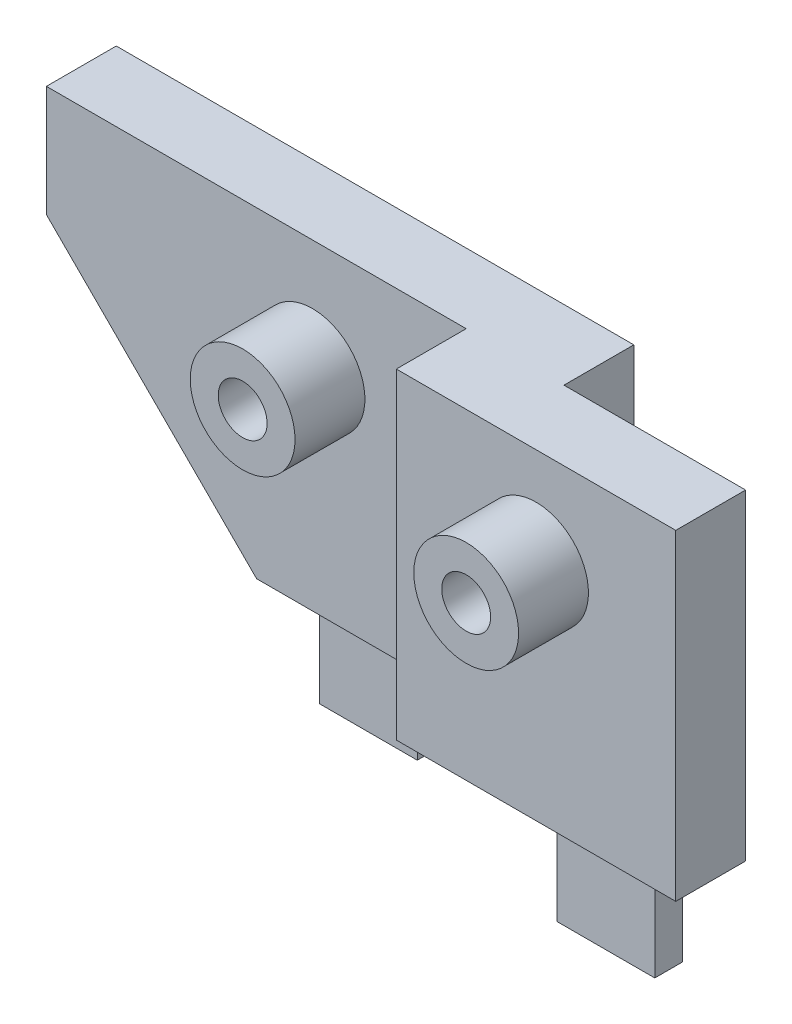
SolidWorks part; units mm, degrees
ref_plane "Front Plane" through (0, 0, 0) normal (0, 0, 1) x (1, 0, 0)
ref_plane "Top Plane" through (0, 0, 0) normal (0, 1, 0) x (1, 0, 0)
ref_plane "Right Plane" through (0, 0, 0) normal (1, 0, 0) x (0, 0, -1)
sketch "Sketch1" plane through (0, 0, 0) normal (0, 1, 0) x (1, 0, 0)
  line L0 (18, 0) -> (22, 0)
  line L1 (0, 0) -> (18, 0)
  line L2 (0, 0) -> (0, -5)
  line L3 (0, -5) -> (15, -5)
  line L4 (18, 0) -> (18, -10) construction
  line L5 (22, -5) -> (35, -5)
  line L6 (15, -5) -> (15, -10)
  line L7 (15, -10) -> (35, -10)
  line L8 (35, -5) -> (35, -10)
  line L9 (22, 0) -> (22, -5)
  dimension "D1" = 5
  dimension "D2" = 18
  dimension "D3" = 5
  dimension "D4" = 20
  dimension "D5" = 15
  dimension "D6" = 5
  dimension "D7" = 7
extrude "Boss-Extrude1" add sketch "Sketch1" along normal blind 23
sketch "Sketch2" plane through (0, 0, 10) normal (0, 0, 1) x (1, 0, 0)
  line L0 (35, 16) -> (25, 16) construction
  line L1 (35, 23) -> (35, 0) construction
  line L2 (15, 0) -> (35, 0) construction
  line L3 (0, 23) -> (0, 0) construction
  line L4 (0, 0) -> (15, 0) construction
  circle A0 centre (4, 15) radius 1.75
  circle A1 centre (25, 16) radius 1.75
  dimension "D5" = 3.5
  dimension "D6" = 3.5
  dimension "D1" = 10
  dimension "D2" = 16
  dimension "D3" = 4
  dimension "D4" = 15
extrude "Cut-Extrude1" cut sketch "Sketch2" against normal blind 10
sketch "Sketch3" plane through (0, 0, 0) normal (0, -1, 0) x (1, 0, 0)
  line L0 (15, 5) -> (22, 5) construction
  line L1 (18.5, 0) -> (18.5, 10) construction
  line L2 (22, 0) -> (0, 0) construction
  line L3 (15, 10) -> (35, 10) construction
  circle A0 centre (18.5, 5) radius 1.5
  point P10 (18.5, 5)
  dimension "D1" = 3
extrude "Cut-Extrude2" cut sketch "Sketch3" against normal blind 10 contours A0
sketch "Sketch4" plane through (0, 0, 0) normal (0, -1, 0) x (1, 0, 0)
  line L0 (0, 2.5) -> (22, 2.5) construction
  line L1 (0, 0) -> (0, 5) construction
  line L2 (22, 5) -> (22, 0) construction
  line L3 (15, 7.5) -> (35, 7.5) construction
  line L4 (15, 5) -> (15, 10) construction
  line L5 (35, 10) -> (35, 5) construction
  line L6 (22, 0) -> (0, 0) construction
  line L7 (10, 1.5) -> (3, 1.5)
  line L8 (10, 1.5) -> (10, 3.5)
  line L9 (10, 3.5) -> (3, 3.5)
  line L10 (3, 1.5) -> (3, 3.5)
  line L11 (10, 1.5) -> (3, 3.5) construction
  line L12 (10, 3.5) -> (3, 1.5) construction
  line L13 (32, 6.5) -> (25, 6.5)
  line L14 (32, 6.5) -> (32, 8.5)
  line L15 (32, 8.5) -> (25, 8.5)
  line L16 (25, 6.5) -> (25, 8.5)
  line L17 (32, 6.5) -> (25, 8.5) construction
  line L18 (32, 8.5) -> (25, 6.5) construction
  circle A0 centre (18.5, 5) radius 1.5 construction
  point P12 (6.5, 2.5)
  point P17 (28.5, 7.5)
  dimension "D8" = 18.5
  dimension "D1" = 2
  dimension "D2" = 7
  dimension "D3" = 3
  dimension "D4" = 2
  dimension "D5" = 7
  dimension "D6" = 3
  dimension "D7" = 35
  dimension "D9" = 5
extrude "Boss-Extrude2" add sketch "Sketch4" along normal blind 7
sketch "Sketch6" plane through (0, 0, 5) normal (0, 0, 1) x (1, 0, 0)
  circle A0 centre (4, 15) radius 1.75
  circle A1 centre (4, 15) radius 3.75
  dimension "D1" = 2
  dimension "D2" = 3.5
extrude "Boss-Extrude3" add sketch "Sketch6" along normal blind 5
sketch "Sketch7" plane through (0, 0, 10) normal (0, 0, 1) x (1, 0, 0)
  circle A0 centre (25, 16) radius 1.75
  circle A1 centre (25, 16) radius 3.75
  dimension "D1" = 3.5
  dimension "D2" = 2
extrude "Boss-Extrude4" add sketch "Sketch7" along normal blind 5 contours A1 | A0
sketch "Sketch10" plane through (0, 0, 5) normal (0, 0, 1) x (1, 0, 0)
  line L0 (0, 23) -> (-15.0472, 23)
  line L1 (-15.0472, 15.0472) -> (0, 0)
  line L2 (0, 23) -> (0, 0) construction
  line L3 (-15.0472, 23) -> (-15.0472, 15.0472)
  line L4 (0, 23) -> (0, 0)
  dimension "D1" = 45
  dimension "D2" = 21.28
extrude "Boss-Extrude5" add sketch "Sketch10" against normal blind 5
